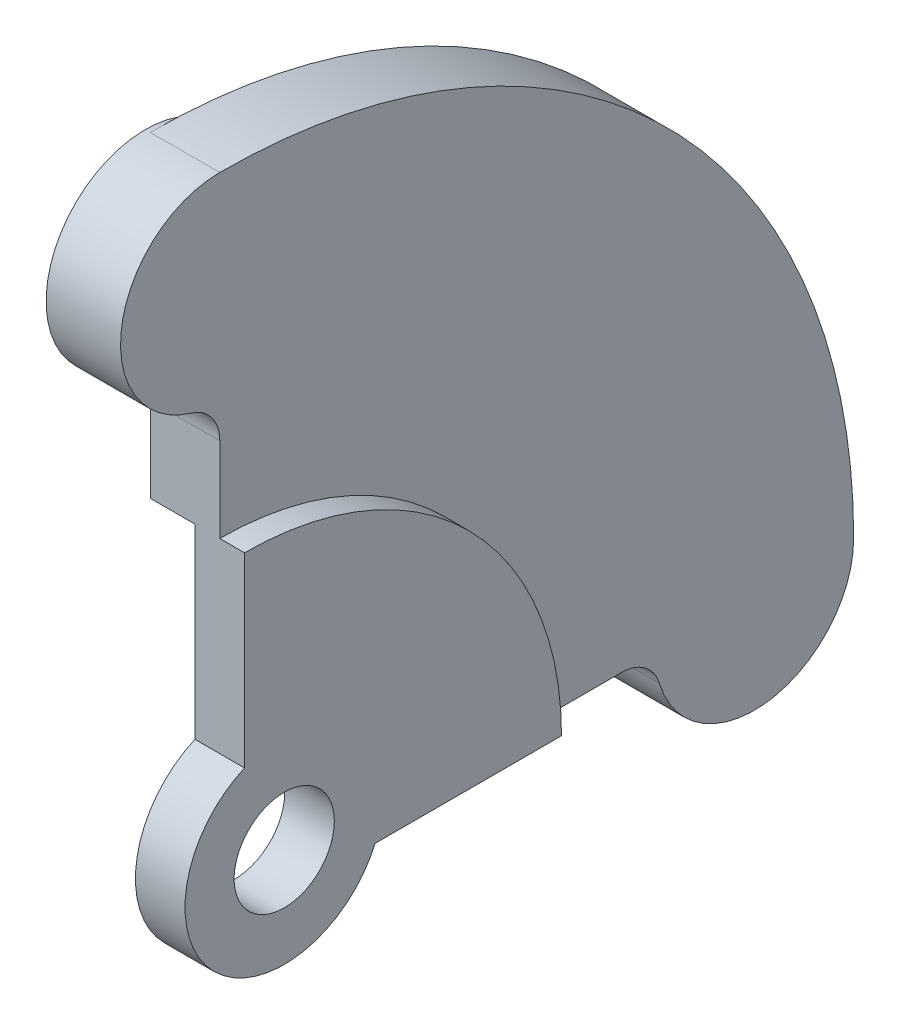
SolidWorks part; units mm, degrees
ref_plane "Alzado" through (0, 0, 0) normal (0, 0, 1) x (1, 0, 0)
ref_plane "Planta" through (0, 0, 0) normal (0, 1, 0) x (1, 0, 0)
ref_plane "Vista lateral" through (0, 0, 0) normal (1, 0, 0) x (0, 0, -1)
sketch "Croquis2" plane through (0, 0, 0) normal (1, 0, 0) x (0, 0, -1)
  line L0 (0, 43.9) -> (0, 0)
  line L1 (0, 0) -> (43.9, 0)
  arc A0 (63.9, 0) -> (0, 63.9) centre (0, 0) ccw
  circle A1 centre (0, 53.9) radius 10
  circle A2 centre (53.9, 0) radius 10
  arc A3 (31.95, 0) -> (0, 31.95) centre (0, 0) ccw
  dimension "D1" = 127.8
  dimension "D2" = 20
  dimension "D3" = 20
  dimension "D4" = 63.9
  dimension "D5" = 53.9
  dimension "D6" = 20
extrude "Saliente-Extruir1" add sketch "Croquis2" along normal mid plane 5 contours L1 A3 L0 region at (0, 13.56, -13.56)
extrude "Saliente-Extruir2" add sketch "Croquis2<3>" against normal blind 7 contours A3 L1 A2 A0 A1 L0 region at (0, 32.0258, -32.0258)
sketch "Croquis2<3>" plane through (0, 0, 0) normal (1, 0, 0) x (0, 0, -1) same geometry as "Croquis2"
extrude "Saliente-Extruir3" add sketch "Croquis2<4>" against normal blind 7.5 contours A1 | A2 region at (0, 53.9, 0) region at (0, 0, -53.9)
sketch "Croquis2<4>" plane through (0, 0, 0) normal (1, 0, 0) x (0, 0, -1) same geometry as "Croquis2"
fillet "Redondeo1" radius 4 1 edges at (0, 0, 0)
fillet "Redondeo2" radius 4 2 edges at (-3.5, 0, -43.9) (-3.5, 43.9, 0)
sketch "Croquis3" plane through (2.5, 0, 0) normal (1, 0, 0) x (0, 0, -1)
  circle A0 centre (4, 4) radius 10
  dimension "D1" = 20
extrude "Saliente-Extruir4" add sketch "Croquis3" against normal up to surface (5 mm away) up to face at (-2.5, 10.4347, -10.4347)
sketch "Croquis4" plane through (2.5, 0, 0) normal (1, 0, 0) x (0, 0, -1)
  circle A0 centre (4, 4) radius 5.05
  dimension "D1" = 10.1
extrude "Cortar-Extruir1" cut sketch "Croquis4" against normal blind 131
